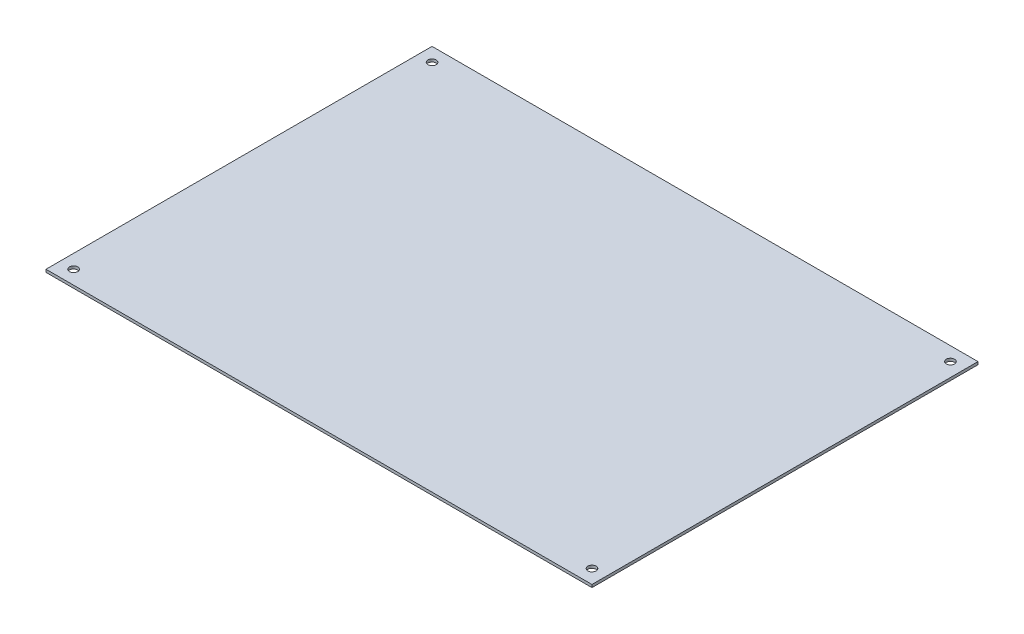
SolidWorks part; units mm, degrees
material "Copper"
ref_plane "Front Plane" through (0, 0, 0) normal (0, 0, 1) x (1, 0, 0)
ref_plane "Top Plane" through (0, 0, 0) normal (0, 1, 0) x (1, 0, 0)
ref_plane "Right Plane" through (0, 0, 0) normal (1, 0, 0) x (0, 0, -1)
sketch "Sketch1" plane through (0, 0, 0) normal (0, 1, 0) x (1, 0, 0)
  line L1 (148.5, -105) -> (-148.5, -105)
  line L2 (148.5, -105) -> (148.5, 105)
  line L3 (148.5, 105) -> (-148.5, 105)
  line L4 (-148.5, -105) -> (-148.5, 105)
  line L5 (148.5, -105) -> (-148.5, 105) construction
  line L6 (148.5, 105) -> (-148.5, -105) construction
  point P0 (0, 0)
  dimension "D1" = 297
  dimension "D2" = 210
extrude "Boss-Extrude1" add sketch "Sketch1" along normal blind 1.5
sketch "Sketch2" plane through (0, 1.5, 0) normal (0, 1, 0) x (1, 0, 0)
  line L0 (-101.7102, 6.397) -> (-102.7298, 6.397)
  line L1 (-102.7298, 6.397) -> (-103.109, 6.0178)
  line L2 (-103.109, 6.0178) -> (-103.109, 3.9822)
  line L3 (-103.109, 3.9822) -> (-102.7298, 3.603)
  line L4 (-102.7298, 3.603) -> (-101.7102, 3.603)
  line L5 (-101.7102, 3.603) -> (-101.331, 3.9822)
  line L6 (-101.331, 3.9822) -> (-101.331, 6.0178)
  line L7 (-101.331, 6.0178) -> (-101.7102, 6.397)
  line L8 (-104.2502, 6.397) -> (-105.2698, 6.397)
  line L9 (-105.2698, 6.397) -> (-105.649, 6.0178)
  line L10 (-105.649, 6.0178) -> (-105.649, 3.9822)
  line L11 (-105.649, 3.9822) -> (-105.2698, 3.603)
  line L12 (-105.2698, 3.603) -> (-104.2502, 3.603)
  line L13 (-104.2502, 3.603) -> (-103.871, 3.9822)
  line L14 (-103.871, 3.9822) -> (-103.871, 6.0178)
  line L15 (-103.871, 6.0178) -> (-104.2502, 6.397)
  line L16 (-106.7902, 6.397) -> (-107.8098, 6.397)
  line L17 (-107.8098, 6.397) -> (-108.189, 6.0178)
  line L18 (-108.189, 6.0178) -> (-108.189, 3.9822)
  line L19 (-108.189, 3.9822) -> (-107.8098, 3.603)
  line L20 (-107.8098, 3.603) -> (-106.7902, 3.603)
  line L21 (-106.7902, 3.603) -> (-106.411, 3.9822)
  line L22 (-106.411, 3.9822) -> (-106.411, 6.0178)
  line L23 (-106.411, 6.0178) -> (-106.7902, 6.397)
  line L24 (-109.3302, 6.397) -> (-110.3498, 6.397)
  line L25 (-110.3498, 6.397) -> (-110.729, 6.0178)
  line L26 (-110.729, 6.0178) -> (-110.729, 3.9822)
  line L27 (-110.729, 3.9822) -> (-110.3498, 3.603)
  line L28 (-110.3498, 3.603) -> (-109.3302, 3.603)
  line L29 (-109.3302, 3.603) -> (-108.951, 3.9822)
  line L30 (-108.951, 3.9822) -> (-108.951, 6.0178)
  line L31 (-108.951, 6.0178) -> (-109.3302, 6.397)
  line L32 (-111.8702, 6.397) -> (-112.8898, 6.397)
  line L33 (-112.8898, 6.397) -> (-113.269, 6.0178)
  line L34 (-113.269, 6.0178) -> (-113.269, 3.9822)
  line L35 (-113.269, 3.9822) -> (-112.8898, 3.603)
  line L36 (-112.8898, 3.603) -> (-111.8702, 3.603)
  line L37 (-111.8702, 3.603) -> (-111.491, 3.9822)
  line L38 (-111.491, 3.9822) -> (-111.491, 6.0178)
  line L39 (-111.491, 6.0178) -> (-111.8702, 6.397)
  line L40 (-114.4102, 6.397) -> (-115.4298, 6.397)
  line L41 (-115.4298, 6.397) -> (-115.809, 6.0178)
  line L42 (-115.809, 6.0178) -> (-115.809, 3.9822)
  line L43 (-115.809, 3.9822) -> (-115.4298, 3.603)
  line L44 (-115.4298, 3.603) -> (-114.4102, 3.603)
  line L45 (-114.4102, 3.603) -> (-114.031, 3.9822)
  line L46 (-114.031, 3.9822) -> (-114.031, 6.0178)
  line L47 (-114.031, 6.0178) -> (-114.4102, 6.397)
  line L48 (-116.9502, 6.397) -> (-117.9698, 6.397)
  line L49 (-117.9698, 6.397) -> (-118.349, 6.0178)
  line L50 (-118.349, 6.0178) -> (-118.349, 3.9822)
  line L51 (-118.349, 3.9822) -> (-117.9698, 3.603)
  line L52 (-117.9698, 3.603) -> (-116.9502, 3.603)
  line L53 (-116.9502, 3.603) -> (-116.571, 3.9822)
  line L54 (-116.571, 3.9822) -> (-116.571, 6.0178)
  line L55 (-116.571, 6.0178) -> (-116.9502, 6.397)
  line L56 (-119.4902, 6.397) -> (-120.5098, 6.397)
  line L57 (-120.5098, 6.397) -> (-120.889, 6.0178)
  line L58 (-120.889, 6.0178) -> (-120.889, 3.9822)
  line L59 (-120.889, 3.9822) -> (-120.5098, 3.603)
  line L60 (-120.5098, 3.603) -> (-119.4902, 3.603)
  line L61 (-119.4902, 3.603) -> (-119.111, 3.9822)
  line L62 (-119.111, 3.9822) -> (-119.111, 6.0178)
  line L63 (-119.111, 6.0178) -> (-119.4902, 6.397)
  line L64 (-97.6498, 6.397) -> (-96.6302, 6.397)
  line L65 (-96.6302, 6.397) -> (-96.251, 6.0178)
  line L66 (-96.251, 6.0178) -> (-96.251, 3.9822)
  line L67 (-96.251, 3.9822) -> (-96.6302, 3.603)
  line L68 (-96.6302, 3.603) -> (-97.6498, 3.603)
  line L69 (-97.6498, 3.603) -> (-98.029, 3.9822)
  line L70 (-98.029, 3.9822) -> (-98.029, 6.0178)
  line L71 (-98.029, 6.0178) -> (-97.6498, 6.397)
  line L72 (-95.1098, 6.397) -> (-94.0902, 6.397)
  line L73 (-94.0902, 6.397) -> (-93.711, 6.0178)
  line L74 (-93.711, 6.0178) -> (-93.711, 3.9822)
  line L75 (-93.711, 3.9822) -> (-94.0902, 3.603)
  line L76 (-94.0902, 3.603) -> (-95.1098, 3.603)
  line L77 (-95.1098, 3.603) -> (-95.489, 3.9822)
  line L78 (-95.489, 3.9822) -> (-95.489, 6.0178)
  line L79 (-95.489, 6.0178) -> (-95.1098, 6.397)
  line L80 (-92.5698, 6.397) -> (-91.5502, 6.397)
  line L81 (-91.5502, 6.397) -> (-91.171, 6.0178)
  line L82 (-91.171, 6.0178) -> (-91.171, 3.9822)
  line L83 (-91.171, 3.9822) -> (-91.5502, 3.603)
  line L84 (-91.5502, 3.603) -> (-92.5698, 3.603)
  line L85 (-92.5698, 3.603) -> (-92.949, 3.9822)
  line L86 (-92.949, 3.9822) -> (-92.949, 6.0178)
  line L87 (-92.949, 6.0178) -> (-92.5698, 6.397)
  line L88 (-90.0298, 6.397) -> (-89.0102, 6.397)
  line L89 (-89.0102, 6.397) -> (-88.631, 6.0178)
  line L90 (-88.631, 6.0178) -> (-88.631, 3.9822)
  line L91 (-88.631, 3.9822) -> (-89.0102, 3.603)
  line L92 (-89.0102, 3.603) -> (-90.0298, 3.603)
  line L93 (-90.0298, 3.603) -> (-90.409, 3.9822)
  line L94 (-90.409, 3.9822) -> (-90.409, 6.0178)
  line L95 (-90.409, 6.0178) -> (-90.0298, 6.397)
  line L96 (-87.4898, 6.397) -> (-86.4702, 6.397)
  line L97 (-86.4702, 6.397) -> (-86.091, 6.0178)
  line L98 (-86.091, 6.0178) -> (-86.091, 3.9822)
  line L99 (-86.091, 3.9822) -> (-86.4702, 3.603)
  line L100 (-86.4702, 3.603) -> (-87.4898, 3.603)
  line L101 (-87.4898, 3.603) -> (-87.869, 3.9822)
  line L102 (-87.869, 3.9822) -> (-87.869, 6.0178)
  line L103 (-87.869, 6.0178) -> (-87.4898, 6.397)
  line L104 (-84.9498, 6.397) -> (-83.9302, 6.397)
  line L105 (-83.9302, 6.397) -> (-83.551, 6.0178)
  line L106 (-83.551, 6.0178) -> (-83.551, 3.9822)
  line L107 (-83.551, 3.9822) -> (-83.9302, 3.603)
  line L108 (-83.9302, 3.603) -> (-84.9498, 3.603)
  line L109 (-84.9498, 3.603) -> (-85.329, 3.9822)
  line L110 (-85.329, 3.9822) -> (-85.329, 6.0178)
  line L111 (-85.329, 6.0178) -> (-84.9498, 6.397)
  line L112 (-83.9302, -41.863) -> (-84.9498, -41.863)
  line L113 (-84.9498, -41.863) -> (-85.329, -42.2422)
  line L114 (-85.329, -42.2422) -> (-85.329, -44.2778)
  line L115 (-85.329, -44.2778) -> (-84.9498, -44.657)
  line L116 (-84.9498, -44.657) -> (-83.9302, -44.657)
  line L117 (-83.9302, -44.657) -> (-83.551, -44.2778)
  line L118 (-83.551, -44.2778) -> (-83.551, -42.2422)
  line L119 (-83.551, -42.2422) -> (-83.9302, -41.863)
  line L120 (-86.4702, -41.863) -> (-87.4898, -41.863)
  line L121 (-87.4898, -41.863) -> (-87.869, -42.2422)
  line L122 (-87.869, -42.2422) -> (-87.869, -44.2778)
  line L123 (-87.869, -44.2778) -> (-87.4898, -44.657)
  line L124 (-87.4898, -44.657) -> (-86.4702, -44.657)
  line L125 (-86.4702, -44.657) -> (-86.091, -44.2778)
  line L126 (-86.091, -44.2778) -> (-86.091, -42.2422)
  line L127 (-86.091, -42.2422) -> (-86.4702, -41.863)
  line L128 (-89.0102, -41.863) -> (-90.0298, -41.863)
  line L129 (-90.0298, -41.863) -> (-90.409, -42.2422)
  line L130 (-90.409, -42.2422) -> (-90.409, -44.2778)
  line L131 (-90.409, -44.2778) -> (-90.0298, -44.657)
  line L132 (-90.0298, -44.657) -> (-89.0102, -44.657)
  line L133 (-89.0102, -44.657) -> (-88.631, -44.2778)
  line L134 (-88.631, -44.2778) -> (-88.631, -42.2422)
  line L135 (-88.631, -42.2422) -> (-89.0102, -41.863)
  line L136 (-91.5502, -41.863) -> (-92.5698, -41.863)
  line L137 (-92.5698, -41.863) -> (-92.949, -42.2422)
  line L138 (-92.949, -42.2422) -> (-92.949, -44.2778)
  line L139 (-92.949, -44.2778) -> (-92.5698, -44.657)
  line L140 (-92.5698, -44.657) -> (-91.5502, -44.657)
  line L141 (-91.5502, -44.657) -> (-91.171, -44.2778)
  line L142 (-91.171, -44.2778) -> (-91.171, -42.2422)
  line L143 (-91.171, -42.2422) -> (-91.5502, -41.863)
  line L144 (-94.0902, -41.863) -> (-95.1098, -41.863)
  line L145 (-95.1098, -41.863) -> (-95.489, -42.2422)
  line L146 (-95.489, -42.2422) -> (-95.489, -44.2778)
  line L147 (-95.489, -44.2778) -> (-95.1098, -44.657)
  line L148 (-95.1098, -44.657) -> (-94.0902, -44.657)
  line L149 (-94.0902, -44.657) -> (-93.711, -44.2778)
  line L150 (-93.711, -44.2778) -> (-93.711, -42.2422)
  line L151 (-93.711, -42.2422) -> (-94.0902, -41.863)
  line L152 (-96.6302, -41.863) -> (-97.6498, -41.863)
  line L153 (-97.6498, -41.863) -> (-98.029, -42.2422)
  line L154 (-98.029, -42.2422) -> (-98.029, -44.2778)
  line L155 (-98.029, -44.2778) -> (-97.6498, -44.657)
  line L156 (-97.6498, -44.657) -> (-96.6302, -44.657)
  line L157 (-96.6302, -44.657) -> (-96.251, -44.2778)
  line L158 (-96.251, -44.2778) -> (-96.251, -42.2422)
  line L159 (-96.251, -42.2422) -> (-96.6302, -41.863)
  line L160 (-99.1702, -41.863) -> (-100.1898, -41.863)
  line L161 (-100.1898, -41.863) -> (-100.569, -42.2422)
  line L162 (-100.569, -42.2422) -> (-100.569, -44.2778)
  line L163 (-100.569, -44.2778) -> (-100.1898, -44.657)
  line L164 (-100.1898, -44.657) -> (-99.1702, -44.657)
  line L165 (-99.1702, -44.657) -> (-98.791, -44.2778)
  line L166 (-98.791, -44.2778) -> (-98.791, -42.2422)
  line L167 (-98.791, -42.2422) -> (-99.1702, -41.863)
  line L168 (-101.7102, -41.863) -> (-102.7298, -41.863)
  line L169 (-102.7298, -41.863) -> (-103.109, -42.2422)
  line L170 (-103.109, -42.2422) -> (-103.109, -44.2778)
  line L171 (-103.109, -44.2778) -> (-102.7298, -44.657)
  line L172 (-102.7298, -44.657) -> (-101.7102, -44.657)
  line L173 (-101.7102, -44.657) -> (-101.331, -44.2778)
  line L174 (-101.331, -44.2778) -> (-101.331, -42.2422)
  line L175 (-101.331, -42.2422) -> (-101.7102, -41.863)
  line L176 (-105.5202, -41.863) -> (-106.5398, -41.863)
  line L177 (-106.5398, -41.863) -> (-106.919, -42.2422)
  line L178 (-106.919, -42.2422) -> (-106.919, -44.2778)
  line L179 (-106.919, -44.2778) -> (-106.5398, -44.657)
  line L180 (-106.5398, -44.657) -> (-105.5202, -44.657)
  line L181 (-105.5202, -44.657) -> (-105.141, -44.2778)
  line L182 (-105.141, -44.2778) -> (-105.141, -42.2422)
  line L183 (-105.141, -42.2422) -> (-105.5202, -41.863)
  line L184 (-108.0602, -41.863) -> (-109.0798, -41.863)
  line L185 (-109.0798, -41.863) -> (-109.459, -42.2422)
  line L186 (-109.459, -42.2422) -> (-109.459, -44.2778)
  line L187 (-109.459, -44.2778) -> (-109.0798, -44.657)
  line L188 (-109.0798, -44.657) -> (-108.0602, -44.657)
  line L189 (-108.0602, -44.657) -> (-107.681, -44.2778)
  line L190 (-107.681, -44.2778) -> (-107.681, -42.2422)
  line L191 (-107.681, -42.2422) -> (-108.0602, -41.863)
  line L192 (-110.6002, -41.863) -> (-111.6198, -41.863)
  line L193 (-111.6198, -41.863) -> (-111.999, -42.2422)
  line L194 (-111.999, -42.2422) -> (-111.999, -44.2778)
  line L195 (-111.999, -44.2778) -> (-111.6198, -44.657)
  line L196 (-111.6198, -44.657) -> (-110.6002, -44.657)
  line L197 (-110.6002, -44.657) -> (-110.221, -44.2778)
  line L198 (-110.221, -44.2778) -> (-110.221, -42.2422)
  line L199 (-110.221, -42.2422) -> (-110.6002, -41.863)
  line L200 (-113.1402, -41.863) -> (-114.1598, -41.863)
  line L201 (-114.1598, -41.863) -> (-114.539, -42.2422)
  line L202 (-114.539, -42.2422) -> (-114.539, -44.2778)
  line L203 (-114.539, -44.2778) -> (-114.1598, -44.657)
  line L204 (-114.1598, -44.657) -> (-113.1402, -44.657)
  line L205 (-113.1402, -44.657) -> (-112.761, -44.2778)
  line L206 (-112.761, -44.2778) -> (-112.761, -42.2422)
  line L207 (-112.761, -42.2422) -> (-113.1402, -41.863)
  line L208 (-115.6802, -41.863) -> (-116.6998, -41.863)
  line L209 (-116.6998, -41.863) -> (-117.079, -42.2422)
  line L210 (-117.079, -42.2422) -> (-117.079, -44.2778)
  line L211 (-117.079, -44.2778) -> (-116.6998, -44.657)
  line L212 (-116.6998, -44.657) -> (-115.6802, -44.657)
  line L213 (-115.6802, -44.657) -> (-115.301, -44.2778)
  line L214 (-115.301, -44.2778) -> (-115.301, -42.2422)
  line L215 (-115.301, -42.2422) -> (-115.6802, -41.863)
  line L216 (-118.2202, -41.863) -> (-119.2398, -41.863)
  line L217 (-119.2398, -41.863) -> (-119.619, -42.2422)
  line L218 (-119.619, -42.2422) -> (-119.619, -44.2778)
  line L219 (-119.619, -44.2778) -> (-119.2398, -44.657)
  line L220 (-119.2398, -44.657) -> (-118.2202, -44.657)
  line L221 (-118.2202, -44.657) -> (-117.841, -44.2778)
  line L222 (-117.841, -44.2778) -> (-117.841, -42.2422)
  line L223 (-117.841, -42.2422) -> (-118.2202, -41.863)
  line L224 (-120.7602, -41.863) -> (-121.7798, -41.863)
  line L225 (-121.7798, -41.863) -> (-122.159, -42.2422)
  line L226 (-122.159, -42.2422) -> (-122.159, -44.2778)
  line L227 (-122.159, -44.2778) -> (-121.7798, -44.657)
  line L228 (-121.7798, -44.657) -> (-120.7602, -44.657)
  line L229 (-120.7602, -44.657) -> (-120.381, -44.2778)
  line L230 (-120.381, -44.2778) -> (-120.381, -42.2422)
  line L231 (-120.381, -42.2422) -> (-120.7602, -41.863)
  line L232 (-123.3002, -41.863) -> (-124.3198, -41.863)
  line L233 (-124.3198, -41.863) -> (-124.699, -42.2422)
  line L234 (-124.699, -42.2422) -> (-124.699, -44.2778)
  line L235 (-124.699, -44.2778) -> (-124.3198, -44.657)
  line L236 (-124.3198, -44.657) -> (-123.3002, -44.657)
  line L237 (-123.3002, -44.657) -> (-122.921, -44.2778)
  line L238 (-122.921, -44.2778) -> (-122.921, -42.2422)
  line L239 (-122.921, -42.2422) -> (-123.3002, -41.863)
  line L240 (-125.8402, -41.863) -> (-126.8598, -41.863)
  line L241 (-126.8598, -41.863) -> (-127.239, -42.2422)
  line L242 (-127.239, -42.2422) -> (-127.239, -44.2778)
  line L243 (-127.239, -44.2778) -> (-126.8598, -44.657)
  line L244 (-126.8598, -44.657) -> (-125.8402, -44.657)
  line L245 (-125.8402, -44.657) -> (-125.461, -44.2778)
  line L246 (-125.461, -44.2778) -> (-125.461, -42.2422)
  line L247 (-125.461, -42.2422) -> (-125.8402, -41.863)
  line L248 (-128.3802, -41.863) -> (-129.3998, -41.863)
  line L249 (-129.3998, -41.863) -> (-129.779, -42.2422)
  line L250 (-129.779, -42.2422) -> (-129.779, -44.2778)
  line L251 (-129.779, -44.2778) -> (-129.3998, -44.657)
  line L252 (-129.3998, -44.657) -> (-128.3802, -44.657)
  line L253 (-128.3802, -44.657) -> (-128.001, -44.2778)
  line L254 (-128.001, -44.2778) -> (-128.001, -42.2422)
  line L255 (-128.001, -42.2422) -> (-128.3802, -41.863)
  line L256 (-4.887, -62.244) -> (-4.887, -64.276)
  line L257 (-4.887, -64.276) -> (-4.8895, -64.302)
  line L258 (-4.8895, -64.302) -> (-4.8968, -64.326)
  line L259 (-4.8968, -64.326) -> (-4.9083, -64.3476)
  line L260 (-4.9083, -64.3476) -> (-4.9237, -64.3663)
  line L261 (-4.9237, -64.3663) -> (-4.9424, -64.3817)
  line L262 (-4.9424, -64.3817) -> (-4.964, -64.3932)
  line L263 (-4.964, -64.3932) -> (-4.988, -64.4005)
  line L264 (-4.988, -64.4005) -> (-5.014, -64.403)
  line L265 (-5.014, -64.403) -> (-7.046, -64.403)
  line L266 (-7.046, -64.403) -> (-7.072, -64.4005)
  line L267 (-7.072, -64.4005) -> (-7.096, -64.3932)
  line L268 (-7.096, -64.3932) -> (-7.1176, -64.3817)
  line L269 (-7.1176, -64.3817) -> (-7.1363, -64.3663)
  line L270 (-7.1363, -64.3663) -> (-7.1516, -64.3476)
  line L271 (-7.1516, -64.3476) -> (-7.1632, -64.326)
  line L272 (-7.1632, -64.326) -> (-7.1705, -64.302)
  line L273 (-7.1705, -64.302) -> (-7.173, -64.276)
  line L274 (-7.173, -64.276) -> (-7.173, -62.244)
  line L275 (-7.173, -62.244) -> (-7.1705, -62.218)
  line L276 (-7.1705, -62.218) -> (-7.1632, -62.194)
  line L277 (-7.1632, -62.194) -> (-7.1516, -62.1724)
  line L278 (-7.1516, -62.1724) -> (-7.1363, -62.1537)
  line L279 (-7.1363, -62.1537) -> (-7.1176, -62.1384)
  line L280 (-7.1176, -62.1384) -> (-7.096, -62.1268)
  line L281 (-7.096, -62.1268) -> (-7.072, -62.1195)
  line L282 (-7.072, -62.1195) -> (-7.046, -62.117)
  line L283 (-7.046, -62.117) -> (-5.014, -62.117)
  line L284 (-5.014, -62.117) -> (-4.988, -62.1195)
  line L285 (-4.988, -62.1195) -> (-4.964, -62.1268)
  line L286 (-4.964, -62.1268) -> (-4.9424, -62.1384)
  line L287 (-4.9424, -62.1384) -> (-4.9237, -62.1537)
  line L288 (-4.9237, -62.1537) -> (-4.9083, -62.1724)
  line L289 (-4.9083, -62.1724) -> (-4.8968, -62.194)
  line L290 (-4.8968, -62.194) -> (-4.8895, -62.218)
  line L291 (-4.8895, -62.218) -> (-4.887, -62.244)
  line L292 (-4.887, -64.784) -> (-4.887, -66.816)
  line L293 (-4.887, -66.816) -> (-4.8895, -66.842)
  line L294 (-4.8895, -66.842) -> (-4.8968, -66.866)
  line L295 (-4.8968, -66.866) -> (-4.9083, -66.8876)
  line L296 (-4.9083, -66.8876) -> (-4.9237, -66.9063)
  line L297 (-4.9237, -66.9063) -> (-4.9424, -66.9217)
  line L298 (-4.9424, -66.9217) -> (-4.964, -66.9332)
  line L299 (-4.964, -66.9332) -> (-4.988, -66.9405)
  line L300 (-4.988, -66.9405) -> (-5.014, -66.943)
  line L301 (-5.014, -66.943) -> (-7.046, -66.943)
  line L302 (-7.046, -66.943) -> (-7.072, -66.9405)
  line L303 (-7.072, -66.9405) -> (-7.096, -66.9332)
  line L304 (-7.096, -66.9332) -> (-7.1176, -66.9217)
  line L305 (-7.1176, -66.9217) -> (-7.1363, -66.9063)
  line L306 (-7.1363, -66.9063) -> (-7.1516, -66.8876)
  line L307 (-7.1516, -66.8876) -> (-7.1632, -66.866)
  line L308 (-7.1632, -66.866) -> (-7.1705, -66.842)
  line L309 (-7.1705, -66.842) -> (-7.173, -66.816)
  line L310 (-7.173, -66.816) -> (-7.173, -64.784)
  line L311 (-7.173, -64.784) -> (-7.1705, -64.758)
  line L312 (-7.1705, -64.758) -> (-7.1632, -64.734)
  line L313 (-7.1632, -64.734) -> (-7.1516, -64.7124)
  line L314 (-7.1516, -64.7124) -> (-7.1363, -64.6937)
  line L315 (-7.1363, -64.6937) -> (-7.1176, -64.6784)
  line L316 (-7.1176, -64.6784) -> (-7.096, -64.6668)
  line L317 (-7.096, -64.6668) -> (-7.072, -64.6595)
  line L318 (-7.072, -64.6595) -> (-7.046, -64.657)
  line L319 (-7.046, -64.657) -> (-5.014, -64.657)
  line L320 (-5.014, -64.657) -> (-4.988, -64.6595)
  line L321 (-4.988, -64.6595) -> (-4.964, -64.6668)
  line L322 (-4.964, -64.6668) -> (-4.9424, -64.6784)
  line L323 (-4.9424, -64.6784) -> (-4.9237, -64.6937)
  line L324 (-4.9237, -64.6937) -> (-4.9083, -64.7124)
  line L325 (-4.9083, -64.7124) -> (-4.8968, -64.734)
  line L326 (-4.8968, -64.734) -> (-4.8895, -64.758)
  line L327 (-4.8895, -64.758) -> (-4.887, -64.784)
  line L328 (15.113, -62.244) -> (15.113, -64.276)
  line L329 (15.113, -64.276) -> (15.1105, -64.302)
  line L330 (15.1105, -64.302) -> (15.1032, -64.326)
  line L331 (15.1032, -64.326) -> (15.0916, -64.3476)
  line L332 (15.0916, -64.3476) -> (15.0763, -64.3663)
  line L333 (15.0763, -64.3663) -> (15.0576, -64.3817)
  line L334 (15.0576, -64.3817) -> (15.036, -64.3932)
  line L335 (15.036, -64.3932) -> (15.012, -64.4005)
  line L336 (15.012, -64.4005) -> (14.986, -64.403)
  line L337 (14.986, -64.403) -> (12.954, -64.403)
  line L338 (12.954, -64.403) -> (12.928, -64.4005)
  line L339 (12.928, -64.4005) -> (12.904, -64.3932)
  line L340 (12.904, -64.3932) -> (12.8824, -64.3817)
  line L341 (12.8824, -64.3817) -> (12.8637, -64.3663)
  line L342 (12.8637, -64.3663) -> (12.8484, -64.3476)
  line L343 (12.8484, -64.3476) -> (12.8368, -64.326)
  line L344 (12.8368, -64.326) -> (12.8295, -64.302)
  line L345 (12.8295, -64.302) -> (12.827, -64.276)
  line L346 (12.827, -64.276) -> (12.827, -62.244)
  line L347 (12.827, -62.244) -> (12.8295, -62.218)
  line L348 (12.8295, -62.218) -> (12.8368, -62.194)
  line L349 (12.8368, -62.194) -> (12.8484, -62.1724)
  line L350 (12.8484, -62.1724) -> (12.8637, -62.1537)
  line L351 (12.8637, -62.1537) -> (12.8824, -62.1384)
  line L352 (12.8824, -62.1384) -> (12.904, -62.1268)
  line L353 (12.904, -62.1268) -> (12.928, -62.1195)
  line L354 (12.928, -62.1195) -> (12.954, -62.117)
  line L355 (12.954, -62.117) -> (14.986, -62.117)
  line L356 (14.986, -62.117) -> (15.012, -62.1195)
  line L357 (15.012, -62.1195) -> (15.036, -62.1268)
  line L358 (15.036, -62.1268) -> (15.0576, -62.1384)
  line L359 (15.0576, -62.1384) -> (15.0763, -62.1537)
  line L360 (15.0763, -62.1537) -> (15.0916, -62.1724)
  line L361 (15.0916, -62.1724) -> (15.1032, -62.194)
  line L362 (15.1032, -62.194) -> (15.1105, -62.218)
  line L363 (15.1105, -62.218) -> (15.113, -62.244)
  line L364 (15.113, -64.784) -> (15.113, -66.816)
  line L365 (15.113, -66.816) -> (15.1105, -66.842)
  line L366 (15.1105, -66.842) -> (15.1032, -66.866)
  line L367 (15.1032, -66.866) -> (15.0916, -66.8876)
  line L368 (15.0916, -66.8876) -> (15.0763, -66.9063)
  line L369 (15.0763, -66.9063) -> (15.0576, -66.9217)
  line L370 (15.0576, -66.9217) -> (15.036, -66.9332)
  line L371 (15.036, -66.9332) -> (15.012, -66.9405)
  line L372 (15.012, -66.9405) -> (14.986, -66.943)
  line L373 (14.986, -66.943) -> (12.954, -66.943)
  line L374 (12.954, -66.943) -> (12.928, -66.9405)
  line L375 (12.928, -66.9405) -> (12.904, -66.9332)
  line L376 (12.904, -66.9332) -> (12.8824, -66.9217)
  line L377 (12.8824, -66.9217) -> (12.8637, -66.9063)
  line L378 (12.8637, -66.9063) -> (12.8484, -66.8876)
  line L379 (12.8484, -66.8876) -> (12.8368, -66.866)
  line L380 (12.8368, -66.866) -> (12.8295, -66.842)
  line L381 (12.8295, -66.842) -> (12.827, -66.816)
  line L382 (12.827, -66.816) -> (12.827, -64.784)
  line L383 (12.827, -64.784) -> (12.8295, -64.758)
  line L384 (12.8295, -64.758) -> (12.8368, -64.734)
  line L385 (12.8368, -64.734) -> (12.8484, -64.7124)
  line L386 (12.8484, -64.7124) -> (12.8637, -64.6937)
  line L387 (12.8637, -64.6937) -> (12.8824, -64.6784)
  line L388 (12.8824, -64.6784) -> (12.904, -64.6668)
  line L389 (12.904, -64.6668) -> (12.928, -64.6595)
  line L390 (12.928, -64.6595) -> (12.954, -64.657)
  line L391 (12.954, -64.657) -> (14.986, -64.657)
  line L392 (14.986, -64.657) -> (15.012, -64.6595)
  line L393 (15.012, -64.6595) -> (15.036, -64.6668)
  line L394 (15.036, -64.6668) -> (15.0576, -64.6784)
  line L395 (15.0576, -64.6784) -> (15.0763, -64.6937)
  line L396 (15.0763, -64.6937) -> (15.0916, -64.7124)
  line L397 (15.0916, -64.7124) -> (15.1032, -64.734)
  line L398 (15.1032, -64.734) -> (15.1105, -64.758)
  line L399 (15.1105, -64.758) -> (15.113, -64.784)
  line L400 (35.113, -62.244) -> (35.113, -64.276)
  line L401 (35.113, -64.276) -> (35.1105, -64.302)
  line L402 (35.1105, -64.302) -> (35.1032, -64.326)
  line L403 (35.1032, -64.326) -> (35.0916, -64.3476)
  line L404 (35.0916, -64.3476) -> (35.0763, -64.3663)
  line L405 (35.0763, -64.3663) -> (35.0576, -64.3817)
  line L406 (35.0576, -64.3817) -> (35.036, -64.3932)
  line L407 (35.036, -64.3932) -> (35.012, -64.4005)
  line L408 (35.012, -64.4005) -> (34.986, -64.403)
  line L409 (34.986, -64.403) -> (32.954, -64.403)
  line L410 (32.954, -64.403) -> (32.928, -64.4005)
  line L411 (32.928, -64.4005) -> (32.904, -64.3932)
  line L412 (32.904, -64.3932) -> (32.8824, -64.3817)
  line L413 (32.8824, -64.3817) -> (32.8637, -64.3663)
  line L414 (32.8637, -64.3663) -> (32.8483, -64.3476)
  line L415 (32.8483, -64.3476) -> (32.8368, -64.326)
  line L416 (32.8368, -64.326) -> (32.8295, -64.302)
  line L417 (32.8295, -64.302) -> (32.827, -64.276)
  line L418 (32.827, -64.276) -> (32.827, -62.244)
  line L419 (32.827, -62.244) -> (32.8295, -62.218)
  line L420 (32.8295, -62.218) -> (32.8368, -62.194)
  line L421 (32.8368, -62.194) -> (32.8483, -62.1724)
  line L422 (32.8483, -62.1724) -> (32.8637, -62.1537)
  line L423 (32.8637, -62.1537) -> (32.8824, -62.1384)
  line L424 (32.8824, -62.1384) -> (32.904, -62.1268)
  line L425 (32.904, -62.1268) -> (32.928, -62.1195)
  line L426 (32.928, -62.1195) -> (32.954, -62.117)
  line L427 (32.954, -62.117) -> (34.986, -62.117)
  line L428 (34.986, -62.117) -> (35.012, -62.1195)
  line L429 (35.012, -62.1195) -> (35.036, -62.1268)
  line L430 (35.036, -62.1268) -> (35.0576, -62.1384)
  line L431 (35.0576, -62.1384) -> (35.0763, -62.1537)
  line L432 (35.0763, -62.1537) -> (35.0916, -62.1724)
  line L433 (35.0916, -62.1724) -> (35.1032, -62.194)
  line L434 (35.1032, -62.194) -> (35.1105, -62.218)
  line L435 (35.1105, -62.218) -> (35.113, -62.244)
  line L436 (35.113, -64.784) -> (35.113, -66.816)
  line L437 (35.113, -66.816) -> (35.1105, -66.842)
  line L438 (35.1105, -66.842) -> (35.1032, -66.866)
  line L439 (35.1032, -66.866) -> (35.0916, -66.8876)
  line L440 (35.0916, -66.8876) -> (35.0763, -66.9063)
  line L441 (35.0763, -66.9063) -> (35.0576, -66.9217)
  line L442 (35.0576, -66.9217) -> (35.036, -66.9332)
  line L443 (35.036, -66.9332) -> (35.012, -66.9405)
  line L444 (35.012, -66.9405) -> (34.986, -66.943)
  line L445 (34.986, -66.943) -> (32.954, -66.943)
  line L446 (32.954, -66.943) -> (32.928, -66.9405)
  line L447 (32.928, -66.9405) -> (32.904, -66.9332)
  line L448 (32.904, -66.9332) -> (32.8824, -66.9217)
  line L449 (32.8824, -66.9217) -> (32.8637, -66.9063)
  line L450 (32.8637, -66.9063) -> (32.8483, -66.8876)
  line L451 (32.8483, -66.8876) -> (32.8368, -66.866)
  line L452 (32.8368, -66.866) -> (32.8295, -66.842)
  line L453 (32.8295, -66.842) -> (32.827, -66.816)
  line L454 (32.827, -66.816) -> (32.827, -64.784)
  line L455 (32.827, -64.784) -> (32.8295, -64.758)
  line L456 (32.8295, -64.758) -> (32.8368, -64.734)
  line L457 (32.8368, -64.734) -> (32.8483, -64.7124)
  line L458 (32.8483, -64.7124) -> (32.8637, -64.6937)
  line L459 (32.8637, -64.6937) -> (32.8824, -64.6784)
  line L460 (32.8824, -64.6784) -> (32.904, -64.6668)
  line L461 (32.904, -64.6668) -> (32.928, -64.6595)
  line L462 (32.928, -64.6595) -> (32.954, -64.657)
  line L463 (32.954, -64.657) -> (34.986, -64.657)
  line L464 (34.986, -64.657) -> (35.012, -64.6595)
  line L465 (35.012, -64.6595) -> (35.036, -64.6668)
  line L466 (35.036, -64.6668) -> (35.0576, -64.6784)
  line L467 (35.0576, -64.6784) -> (35.0763, -64.6937)
  line L468 (35.0763, -64.6937) -> (35.0916, -64.7124)
  line L469 (35.0916, -64.7124) -> (35.1032, -64.734)
  line L470 (35.1032, -64.734) -> (35.1105, -64.758)
  line L471 (35.1105, -64.758) -> (35.113, -64.784)
  line L472 (55.113, -62.244) -> (55.113, -64.276)
  line L473 (55.113, -64.276) -> (55.1105, -64.302)
  line L474 (55.1105, -64.302) -> (55.1032, -64.326)
  line L475 (55.1032, -64.326) -> (55.0917, -64.3476)
  line L476 (55.0917, -64.3476) -> (55.0763, -64.3663)
  line L477 (55.0763, -64.3663) -> (55.0576, -64.3817)
  line L478 (55.0576, -64.3817) -> (55.036, -64.3932)
  line L479 (55.036, -64.3932) -> (55.012, -64.4005)
  line L480 (55.012, -64.4005) -> (54.986, -64.403)
  line L481 (54.986, -64.403) -> (52.954, -64.403)
  line L482 (52.954, -64.403) -> (52.928, -64.4005)
  line L483 (52.928, -64.4005) -> (52.904, -64.3932)
  line L484 (52.904, -64.3932) -> (52.8824, -64.3817)
  line L485 (52.8824, -64.3817) -> (52.8637, -64.3663)
  line L486 (52.8637, -64.3663) -> (52.8484, -64.3476)
  line L487 (52.8484, -64.3476) -> (52.8368, -64.326)
  line L488 (52.8368, -64.326) -> (52.8295, -64.302)
  line L489 (52.8295, -64.302) -> (52.827, -64.276)
  line L490 (52.827, -64.276) -> (52.827, -62.244)
  line L491 (52.827, -62.244) -> (52.8295, -62.218)
  line L492 (52.8295, -62.218) -> (52.8368, -62.194)
  line L493 (52.8368, -62.194) -> (52.8484, -62.1724)
  line L494 (52.8484, -62.1724) -> (52.8637, -62.1537)
  line L495 (52.8637, -62.1537) -> (52.8824, -62.1384)
  line L496 (52.8824, -62.1384) -> (52.904, -62.1268)
  line L497 (52.904, -62.1268) -> (52.928, -62.1195)
  line L498 (52.928, -62.1195) -> (52.954, -62.117)
  line L499 (52.954, -62.117) -> (54.986, -62.117)
  line L500 (54.986, -62.117) -> (55.012, -62.1195)
  line L501 (55.012, -62.1195) -> (55.036, -62.1268)
  line L502 (55.036, -62.1268) -> (55.0576, -62.1384)
  line L503 (55.0576, -62.1384) -> (55.0763, -62.1537)
  line L504 (55.0763, -62.1537) -> (55.0917, -62.1724)
  line L505 (55.0917, -62.1724) -> (55.1032, -62.194)
  line L506 (55.1032, -62.194) -> (55.1105, -62.218)
  line L507 (55.1105, -62.218) -> (55.113, -62.244)
  line L508 (55.113, -64.784) -> (55.113, -66.816)
  line L509 (55.113, -66.816) -> (55.1105, -66.842)
  line L510 (55.1105, -66.842) -> (55.1032, -66.866)
  line L511 (55.1032, -66.866) -> (55.0917, -66.8876)
  line L512 (55.0917, -66.8876) -> (55.0763, -66.9063)
  line L513 (55.0763, -66.9063) -> (55.0576, -66.9217)
  line L514 (55.0576, -66.9217) -> (55.036, -66.9332)
  line L515 (55.036, -66.9332) -> (55.012, -66.9405)
  line L516 (55.012, -66.9405) -> (54.986, -66.943)
  line L517 (54.986, -66.943) -> (52.954, -66.943)
  line L518 (52.954, -66.943) -> (52.928, -66.9405)
  line L519 (52.928, -66.9405) -> (52.904, -66.9332)
  line L520 (52.904, -66.9332) -> (52.8824, -66.9217)
  line L521 (52.8824, -66.9217) -> (52.8637, -66.9063)
  line L522 (52.8637, -66.9063) -> (52.8484, -66.8876)
  line L523 (52.8484, -66.8876) -> (52.8368, -66.866)
  line L524 (52.8368, -66.866) -> (52.8295, -66.842)
  line L525 (52.8295, -66.842) -> (52.827, -66.816)
  line L526 (52.827, -66.816) -> (52.827, -64.784)
  line L527 (52.827, -64.784) -> (52.8295, -64.758)
  line L528 (52.8295, -64.758) -> (52.8368, -64.734)
  line L529 (52.8368, -64.734) -> (52.8484, -64.7124)
  line L530 (52.8484, -64.7124) -> (52.8637, -64.6937)
  line L531 (52.8637, -64.6937) -> (52.8824, -64.6784)
  line L532 (52.8824, -64.6784) -> (52.904, -64.6668)
  line L533 (52.904, -64.6668) -> (52.928, -64.6595)
  line L534 (52.928, -64.6595) -> (52.954, -64.657)
  line L535 (52.954, -64.657) -> (54.986, -64.657)
  line L536 (54.986, -64.657) -> (55.012, -64.6595)
  line L537 (55.012, -64.6595) -> (55.036, -64.6668)
  line L538 (55.036, -64.6668) -> (55.0576, -64.6784)
  line L539 (55.0576, -64.6784) -> (55.0763, -64.6937)
  line L540 (55.0763, -64.6937) -> (55.0917, -64.7124)
  line L541 (55.0917, -64.7124) -> (55.1032, -64.734)
  line L542 (55.1032, -64.734) -> (55.1105, -64.758)
  line L543 (55.1105, -64.758) -> (55.113, -64.784)
  line L544 (75.113, -62.244) -> (75.113, -64.276)
  line L545 (75.113, -64.276) -> (75.1105, -64.302)
  line L546 (75.1105, -64.302) -> (75.1032, -64.326)
  line L547 (75.1032, -64.326) -> (75.0916, -64.3476)
  line L548 (75.0916, -64.3476) -> (75.0763, -64.3663)
  line L549 (75.0763, -64.3663) -> (75.0576, -64.3817)
  line L550 (75.0576, -64.3817) -> (75.036, -64.3932)
  line L551 (75.036, -64.3932) -> (75.012, -64.4005)
  line L552 (75.012, -64.4005) -> (74.986, -64.403)
  line L553 (74.986, -64.403) -> (72.954, -64.403)
  line L554 (72.954, -64.403) -> (72.928, -64.4005)
  line L555 (72.928, -64.4005) -> (72.904, -64.3932)
  line L556 (72.904, -64.3932) -> (72.8824, -64.3817)
  line L557 (72.8824, -64.3817) -> (72.8637, -64.3663)
  line L558 (72.8637, -64.3663) -> (72.8483, -64.3476)
  line L559 (72.8483, -64.3476) -> (72.8368, -64.326)
  line L560 (72.8368, -64.326) -> (72.8295, -64.302)
  line L561 (72.8295, -64.302) -> (72.827, -64.276)
  line L562 (72.827, -64.276) -> (72.827, -62.244)
  line L563 (72.827, -62.244) -> (72.8295, -62.218)
  line L564 (72.8295, -62.218) -> (72.8368, -62.194)
  line L565 (72.8368, -62.194) -> (72.8483, -62.1724)
  line L566 (72.8483, -62.1724) -> (72.8637, -62.1537)
  line L567 (72.8637, -62.1537) -> (72.8824, -62.1384)
  line L568 (72.8824, -62.1384) -> (72.904, -62.1268)
  line L569 (72.904, -62.1268) -> (72.928, -62.1195)
  line L570 (72.928, -62.1195) -> (72.954, -62.117)
  line L571 (72.954, -62.117) -> (74.986, -62.117)
  line L572 (74.986, -62.117) -> (75.012, -62.1195)
  line L573 (75.012, -62.1195) -> (75.036, -62.1268)
  line L574 (75.036, -62.1268) -> (75.0576, -62.1384)
  line L575 (75.0576, -62.1384) -> (75.0763, -62.1537)
  line L576 (75.0763, -62.1537) -> (75.0916, -62.1724)
  line L577 (75.0916, -62.1724) -> (75.1032, -62.194)
  line L578 (75.1032, -62.194) -> (75.1105, -62.218)
  line L579 (75.1105, -62.218) -> (75.113, -62.244)
  line L580 (75.113, -64.784) -> (75.113, -66.816)
  line L581 (75.113, -66.816) -> (75.1105, -66.842)
  line L582 (75.1105, -66.842) -> (75.1032, -66.866)
  line L583 (75.1032, -66.866) -> (75.0916, -66.8876)
  line L584 (75.0916, -66.8876) -> (75.0763, -66.9063)
  line L585 (75.0763, -66.9063) -> (75.0576, -66.9217)
  line L586 (75.0576, -66.9217) -> (75.036, -66.9332)
  line L587 (75.036, -66.9332) -> (75.012, -66.9405)
  line L588 (75.012, -66.9405) -> (74.986, -66.943)
  line L589 (74.986, -66.943) -> (72.954, -66.943)
  line L590 (72.954, -66.943) -> (72.928, -66.9405)
  line L591 (72.928, -66.9405) -> (72.904, -66.9332)
  line L592 (72.904, -66.9332) -> (72.8824, -66.9217)
  line L593 (72.8824, -66.9217) -> (72.8637, -66.9063)
  line L594 (72.8637, -66.9063) -> (72.8483, -66.8876)
  line L595 (72.8483, -66.8876) -> (72.8368, -66.866)
  line L596 (72.8368, -66.866) -> (72.8295, -66.842)
  line L597 (72.8295, -66.842) -> (72.827, -66.816)
  line L598 (72.827, -66.816) -> (72.827, -64.784)
  line L599 (72.827, -64.784) -> (72.8295, -64.758)
  line L600 (72.8295, -64.758) -> (72.8368, -64.734)
  line L601 (72.8368, -64.734) -> (72.8483, -64.7124)
  line L602 (72.8483, -64.7124) -> (72.8637, -64.6937)
  line L603 (72.8637, -64.6937) -> (72.8824, -64.6784)
  line L604 (72.8824, -64.6784) -> (72.904, -64.6668)
  line L605 (72.904, -64.6668) -> (72.928, -64.6595)
  line L606 (72.928, -64.6595) -> (72.954, -64.657)
  line L607 (72.954, -64.657) -> (74.986, -64.657)
  line L608 (74.986, -64.657) -> (75.012, -64.6595)
  line L609 (75.012, -64.6595) -> (75.036, -64.6668)
  line L610 (75.036, -64.6668) -> (75.0576, -64.6784)
  line L611 (75.0576, -64.6784) -> (75.0763, -64.6937)
  line L612 (75.0763, -64.6937) -> (75.0916, -64.7124)
  line L613 (75.0916, -64.7124) -> (75.1032, -64.734)
  line L614 (75.1032, -64.734) -> (75.1105, -64.758)
  line L615 (75.1105, -64.758) -> (75.113, -64.784)
  line L616 (95.113, -62.244) -> (95.113, -64.276)
  line L617 (95.113, -64.276) -> (95.1105, -64.302)
  line L618 (95.1105, -64.302) -> (95.1032, -64.326)
  line L619 (95.1032, -64.326) -> (95.0917, -64.3476)
  line L620 (95.0917, -64.3476) -> (95.0763, -64.3663)
  line L621 (95.0763, -64.3663) -> (95.0576, -64.3817)
  line L622 (95.0576, -64.3817) -> (95.036, -64.3932)
  line L623 (95.036, -64.3932) -> (95.012, -64.4005)
  line L624 (95.012, -64.4005) -> (94.986, -64.403)
  line L625 (94.986, -64.403) -> (92.954, -64.403)
  line L626 (92.954, -64.403) -> (92.928, -64.4005)
  line L627 (92.928, -64.4005) -> (92.904, -64.3932)
  line L628 (92.904, -64.3932) -> (92.8824, -64.3817)
  line L629 (92.8824, -64.3817) -> (92.8637, -64.3663)
  line L630 (92.8637, -64.3663) -> (92.8484, -64.3476)
  line L631 (92.8484, -64.3476) -> (92.8368, -64.326)
  line L632 (92.8368, -64.326) -> (92.8295, -64.302)
  line L633 (92.8295, -64.302) -> (92.827, -64.276)
  line L634 (92.827, -64.276) -> (92.827, -62.244)
  line L635 (92.827, -62.244) -> (92.8295, -62.218)
  line L636 (92.8295, -62.218) -> (92.8368, -62.194)
  line L637 (92.8368, -62.194) -> (92.8484, -62.1724)
  line L638 (92.8484, -62.1724) -> (92.8637, -62.1537)
  line L639 (92.8637, -62.1537) -> (92.8824, -62.1384)
  line L640 (92.8824, -62.1384) -> (92.904, -62.1268)
  line L641 (92.904, -62.1268) -> (92.928, -62.1195)
  line L642 (92.928, -62.1195) -> (92.954, -62.117)
  line L643 (92.954, -62.117) -> (94.986, -62.117)
  line L644 (94.986, -62.117) -> (95.012, -62.1195)
  line L645 (95.012, -62.1195) -> (95.036, -62.1268)
  line L646 (95.036, -62.1268) -> (95.0576, -62.1384)
  line L647 (95.0576, -62.1384) -> (95.0763, -62.1537)
  line L648 (95.0763, -62.1537) -> (95.0917, -62.1724)
  line L649 (95.0917, -62.1724) -> (95.1032, -62.194)
  line L650 (95.1032, -62.194) -> (95.1105, -62.218)
  line L651 (95.1105, -62.218) -> (95.113, -62.244)
  line L652 (95.113, -64.784) -> (95.113, -66.816)
  line L653 (95.113, -66.816) -> (95.1105, -66.842)
  line L654 (95.1105, -66.842) -> (95.1032, -66.866)
  line L655 (95.1032, -66.866) -> (95.0917, -66.8876)
  line L656 (95.0917, -66.8876) -> (95.0763, -66.9063)
  line L657 (95.0763, -66.9063) -> (95.0576, -66.9217)
  line L658 (95.0576, -66.9217) -> (95.036, -66.9332)
  line L659 (95.036, -66.9332) -> (95.012, -66.9405)
  line L660 (95.012, -66.9405) -> (94.986, -66.943)
  line L661 (94.986, -66.943) -> (92.954, -66.943)
  line L662 (92.954, -66.943) -> (92.928, -66.9405)
  line L663 (92.928, -66.9405) -> (92.904, -66.9332)
  line L664 (92.904, -66.9332) -> (92.8824, -66.9217)
  line L665 (92.8824, -66.9217) -> (92.8637, -66.9063)
  line L666 (92.8637, -66.9063) -> (92.8484, -66.8876)
  line L667 (92.8484, -66.8876) -> (92.8368, -66.866)
  line L668 (92.8368, -66.866) -> (92.8295, -66.842)
  line L669 (92.8295, -66.842) -> (92.827, -66.816)
  line L670 (92.827, -66.816) -> (92.827, -64.784)
  line L671 (92.827, -64.784) -> (92.8295, -64.758)
  line L672 (92.8295, -64.758) -> (92.8368, -64.734)
  line L673 (92.8368, -64.734) -> (92.8484, -64.7124)
  line L674 (92.8484, -64.7124) -> (92.8637, -64.6937)
  line L675 (92.8637, -64.6937) -> (92.8824, -64.6784)
  line L676 (92.8824, -64.6784) -> (92.904, -64.6668)
  line L677 (92.904, -64.6668) -> (92.928, -64.6595)
  line L678 (92.928, -64.6595) -> (92.954, -64.657)
  line L679 (92.954, -64.657) -> (94.986, -64.657)
  line L680 (94.986, -64.657) -> (95.012, -64.6595)
  line L681 (95.012, -64.6595) -> (95.036, -64.6668)
  line L682 (95.036, -64.6668) -> (95.0576, -64.6784)
  line L683 (95.0576, -64.6784) -> (95.0763, -64.6937)
  line L684 (95.0763, -64.6937) -> (95.0917, -64.7124)
  line L685 (95.0917, -64.7124) -> (95.1032, -64.734)
  line L686 (95.1032, -64.734) -> (95.1105, -64.758)
  line L687 (95.1105, -64.758) -> (95.113, -64.784)
  line L688 (44.5598, 68.137) -> (43.5402, 68.137)
  line L689 (43.5402, 68.137) -> (43.161, 67.7578)
  line L690 (43.161, 67.7578) -> (43.161, 65.7222)
  line L691 (43.161, 65.7222) -> (43.5402, 65.343)
  line L692 (43.5402, 65.343) -> (44.5598, 65.343)
  line L693 (44.5598, 65.343) -> (44.939, 65.7222)
  line L694 (44.939, 65.7222) -> (44.939, 67.7578)
  line L695 (44.939, 67.7578) -> (44.5598, 68.137)
  line L696 (42.0198, 68.137) -> (41.0002, 68.137)
  line L697 (41.0002, 68.137) -> (40.621, 67.7578)
  line L698 (40.621, 67.7578) -> (40.621, 65.7222)
  line L699 (40.621, 65.7222) -> (41.0002, 65.343)
  line L700 (41.0002, 65.343) -> (42.0198, 65.343)
  line L701 (42.0198, 65.343) -> (42.399, 65.7222)
  line L702 (42.399, 65.7222) -> (42.399, 67.7578)
  line L703 (42.399, 67.7578) -> (42.0198, 68.137)
  line L704 (39.4798, 68.137) -> (38.4602, 68.137)
  line L705 (38.4602, 68.137) -> (38.081, 67.7578)
  line L706 (38.081, 67.7578) -> (38.081, 65.7222)
  line L707 (38.081, 65.7222) -> (38.4602, 65.343)
  line L708 (38.4602, 65.343) -> (39.4798, 65.343)
  line L709 (39.4798, 65.343) -> (39.859, 65.7222)
  line L710 (39.859, 65.7222) -> (39.859, 67.7578)
  line L711 (39.859, 67.7578) -> (39.4798, 68.137)
  line L712 (36.9398, 68.137) -> (35.9202, 68.137)
  line L713 (35.9202, 68.137) -> (35.541, 67.7578)
  line L714 (35.541, 67.7578) -> (35.541, 65.7222)
  line L715 (35.541, 65.7222) -> (35.9202, 65.343)
  line L716 (35.9202, 65.343) -> (36.9398, 65.343)
  line L717 (36.9398, 65.343) -> (37.319, 65.7222)
  line L718 (37.319, 65.7222) -> (37.319, 67.7578)
  line L719 (37.319, 67.7578) -> (36.9398, 68.137)
  line L720 (34.3998, 68.137) -> (33.3802, 68.137)
  line L721 (33.3802, 68.137) -> (33.001, 67.7578)
  line L722 (33.001, 67.7578) -> (33.001, 65.7222)
  line L723 (33.001, 65.7222) -> (33.3802, 65.343)
  line L724 (33.3802, 65.343) -> (34.3998, 65.343)
  line L725 (34.3998, 65.343) -> (34.779, 65.7222)
  line L726 (34.779, 65.7222) -> (34.779, 67.7578)
  line L727 (34.779, 67.7578) -> (34.3998, 68.137)
  line L728 (31.8598, 68.137) -> (30.8402, 68.137)
  line L729 (30.8402, 68.137) -> (30.461, 67.7578)
  line L730 (30.461, 67.7578) -> (30.461, 65.7222)
  line L731 (30.461, 65.7222) -> (30.8402, 65.343)
  line L732 (30.8402, 65.343) -> (31.8598, 65.343)
  line L733 (31.8598, 65.343) -> (32.239, 65.7222)
  line L734 (32.239, 65.7222) -> (32.239, 67.7578)
  line L735 (32.239, 67.7578) -> (31.8598, 68.137)
  line L736 (29.3198, 68.137) -> (28.3002, 68.137)
  line L737 (28.3002, 68.137) -> (27.921, 67.7578)
  line L738 (27.921, 67.7578) -> (27.921, 65.7222)
  line L739 (27.921, 65.7222) -> (28.3002, 65.343)
  line L740 (28.3002, 65.343) -> (29.3198, 65.343)
  line L741 (29.3198, 65.343) -> (29.699, 65.7222)
  line L742 (29.699, 65.7222) -> (29.699, 67.7578)
  line L743 (29.699, 67.7578) -> (29.3198, 68.137)
  line L744 (26.7798, 68.137) -> (25.7602, 68.137)
  line L745 (25.7602, 68.137) -> (25.381, 67.7578)
  line L746 (25.381, 67.7578) -> (25.381, 65.7222)
  line L747 (25.381, 65.7222) -> (25.7602, 65.343)
  line L748 (25.7602, 65.343) -> (26.7798, 65.343)
  line L749 (26.7798, 65.343) -> (27.159, 65.7222)
  line L750 (27.159, 65.7222) -> (27.159, 67.7578)
  line L751 (27.159, 67.7578) -> (26.7798, 68.137)
  line L752 (24.2798, 68.137) -> (23.2602, 68.137)
  line L753 (23.2602, 68.137) -> (22.881, 67.7578)
  line L754 (22.881, 67.7578) -> (22.881, 65.7222)
  line L755 (22.881, 65.7222) -> (23.2602, 65.343)
  line L756 (23.2602, 65.343) -> (24.2798, 65.343)
  line L757 (24.2798, 65.343) -> (24.659, 65.7222)
  line L758 (24.659, 65.7222) -> (24.659, 67.7578)
  line L759 (24.659, 67.7578) -> (24.2798, 68.137)
  line L760 (21.7398, 68.137) -> (20.7202, 68.137)
  line L761 (20.7202, 68.137) -> (20.341, 67.7578)
  line L762 (20.341, 67.7578) -> (20.341, 65.7222)
  line L763 (20.341, 65.7222) -> (20.7202, 65.343)
  line L764 (20.7202, 65.343) -> (21.7398, 65.343)
  line L765 (21.7398, 65.343) -> (22.119, 65.7222)
  line L766 (22.119, 65.7222) -> (22.119, 67.7578)
  line L767 (22.119, 67.7578) -> (21.7398, 68.137)
  line L768 (19.1998, 68.137) -> (18.1802, 68.137)
  line L769 (18.1802, 68.137) -> (17.801, 67.7578)
  line L770 (17.801, 67.7578) -> (17.801, 65.7222)
  line L771 (17.801, 65.7222) -> (18.1802, 65.343)
  line L772 (18.1802, 65.343) -> (19.1998, 65.343)
  line L773 (19.1998, 65.343) -> (19.579, 65.7222)
  line L774 (19.579, 65.7222) -> (19.579, 67.7578)
  line L775 (19.579, 67.7578) -> (19.1998, 68.137)
  line L776 (16.6598, 68.137) -> (15.6402, 68.137)
  line L777 (15.6402, 68.137) -> (15.261, 67.7578)
  line L778 (15.261, 67.7578) -> (15.261, 65.7222)
  line L779 (15.261, 65.7222) -> (15.6402, 65.343)
  line L780 (15.6402, 65.343) -> (16.6598, 65.343)
  line L781 (16.6598, 65.343) -> (17.039, 65.7222)
  line L782 (17.039, 65.7222) -> (17.039, 67.7578)
  line L783 (17.039, 67.7578) -> (16.6598, 68.137)
  line L784 (14.1198, 68.137) -> (13.1002, 68.137)
  line L785 (13.1002, 68.137) -> (12.721, 67.7578)
  line L786 (12.721, 67.7578) -> (12.721, 65.7222)
  line L787 (12.721, 65.7222) -> (13.1002, 65.343)
  line L788 (13.1002, 65.343) -> (14.1198, 65.343)
  line L789 (14.1198, 65.343) -> (14.499, 65.7222)
  line L790 (14.499, 65.7222) -> (14.499, 67.7578)
  line L791 (14.499, 67.7578) -> (14.1198, 68.137)
  line L792 (11.5798, 68.137) -> (10.5602, 68.137)
  line L793 (10.5602, 68.137) -> (10.181, 67.7578)
  line L794 (10.181, 67.7578) -> (10.181, 65.7222)
  line L795 (10.181, 65.7222) -> (10.5602, 65.343)
  line L796 (10.5602, 65.343) -> (11.5798, 65.343)
  line L797 (11.5798, 65.343) -> (11.959, 65.7222)
  line L798 (11.959, 65.7222) -> (11.959, 67.7578)
  line L799 (11.959, 67.7578) -> (11.5798, 68.137)
  line L800 (9.0398, 68.137) -> (8.0202, 68.137)
  line L801 (8.0202, 68.137) -> (7.641, 67.7578)
  line L802 (7.641, 67.7578) -> (7.641, 65.7222)
  line L803 (7.641, 65.7222) -> (8.0202, 65.343)
  line L804 (8.0202, 65.343) -> (9.0398, 65.343)
  line L805 (9.0398, 65.343) -> (9.419, 65.7222)
  line L806 (9.419, 65.7222) -> (9.419, 67.7578)
  line L807 (9.419, 67.7578) -> (9.0398, 68.137)
  line L808 (6.4998, 68.137) -> (5.4802, 68.137)
  line L809 (5.4802, 68.137) -> (5.101, 67.7578)
  line L810 (5.101, 67.7578) -> (5.101, 65.7222)
  line L811 (5.101, 65.7222) -> (5.4802, 65.343)
  line L812 (5.4802, 65.343) -> (6.4998, 65.343)
  line L813 (6.4998, 65.343) -> (6.879, 65.7222)
  line L814 (6.879, 65.7222) -> (6.879, 67.7578)
  line L815 (6.879, 67.7578) -> (6.4998, 68.137)
  line L816 (-121.27, 3.095) -> (-100.95, 3.095)
  line L817 (-100.95, 3.095) -> (-100.95, 6.905)
  line L818 (-100.95, 6.905) -> (-121.27, 6.905)
  line L819 (-121.27, 6.905) -> (-121.27, 3.095)
  line L820 (-107.935, 7.159) -> (-114.412, 7.159) construction
  line L821 (-98.41, 3.095) -> (-83.17, 3.095)
  line L822 (-83.17, 3.095) -> (-83.17, 6.905)
  line L823 (-83.17, 6.905) -> (-98.41, 6.905)
  line L824 (-98.41, 6.905) -> (-98.41, 3.095)
  line L825 (-103.49, -45.165) -> (-83.17, -45.165)
  line L826 (-83.17, -45.165) -> (-83.17, -41.355)
  line L827 (-83.17, -41.355) -> (-103.49, -41.355)
  line L828 (-103.49, -41.355) -> (-103.49, -45.165)
  line L829 (-90.79, -41.101) -> (-95.4382, -41.101) construction
  line L830 (-130.16, -45.165) -> (-104.76, -45.165)
  line L831 (-104.76, -45.165) -> (-104.76, -41.355)
  line L832 (-104.76, -41.355) -> (-130.16, -41.355)
  line L833 (-130.16, -41.355) -> (-130.16, -45.165)
  line L834 (-114.285, -41.101) -> (-119.9619, -41.101) construction
  line L835 (-3.49, -61.355) -> (-3.49, -62.625)
  line L836 (-2.855, -61.99) -> (-4.125, -61.99)
  line L837 (-1.3818, -65.4825) -> (-1.3818, -63.4632) construction
  line L838 (16.51, -61.355) -> (16.51, -62.625)
  line L839 (17.145, -61.99) -> (15.875, -61.99)
  line L840 (18.6182, -65.4825) -> (18.6182, -63.0441) construction
  line L841 (36.51, -61.355) -> (36.51, -62.625)
  line L842 (37.145, -61.99) -> (35.875, -61.99)
  line L843 (38.6182, -65.4825) -> (38.6182, -63.0441) construction
  line L844 (56.51, -61.355) -> (56.51, -62.625)
  line L845 (57.145, -61.99) -> (55.875, -61.99)
  line L846 (58.6182, -65.4825) -> (58.6182, -63.0441) construction
  line L847 (76.51, -61.355) -> (76.51, -62.625)
  line L848 (77.145, -61.99) -> (75.875, -61.99)
  line L849 (78.6182, -65.4825) -> (78.6182, -63.0441) construction
  line L850 (96.51, -61.355) -> (96.51, -62.625)
  line L851 (97.145, -61.99) -> (95.875, -61.99)
  line L852 (98.6182, -65.4825) -> (98.6182, -63.0441) construction
  line L853 (-6.03, -47.03) -> (-6.03, -48.3)
  line L854 (-6.665, -53.38) -> (-5.395, -53.38)
  line L855 (-5.395, -53.38) -> (-5.395, -48.3)
  line L856 (-5.395, -48.3) -> (-6.665, -48.3)
  line L857 (-6.665, -48.3) -> (-6.665, -53.38)
  line L858 (-6.03, -53.38) -> (-6.03, -54.65)
  line L859 (-3.9218, -52.11) -> (-3.9218, -50.0907) construction
  line L860 (13.97, -47.03) -> (13.97, -48.3)
  line L861 (13.335, -53.38) -> (14.605, -53.38)
  line L862 (14.605, -53.38) -> (14.605, -48.3)
  line L863 (14.605, -48.3) -> (13.335, -48.3)
  line L864 (13.335, -48.3) -> (13.335, -53.38)
  line L865 (13.97, -53.38) -> (13.97, -54.65)
  line L866 (16.0782, -52.11) -> (16.0782, -49.6716) construction
  line L867 (33.97, -47.03) -> (33.97, -48.3)
  line L868 (33.335, -53.38) -> (34.605, -53.38)
  line L869 (34.605, -53.38) -> (34.605, -48.3)
  line L870 (34.605, -48.3) -> (33.335, -48.3)
  line L871 (33.335, -48.3) -> (33.335, -53.38)
  line L872 (33.97, -53.38) -> (33.97, -54.65)
  line L873 (36.0782, -52.11) -> (36.0782, -49.6716) construction
  line L874 (53.97, -47.03) -> (53.97, -48.3)
  line L875 (53.335, -53.38) -> (54.605, -53.38)
  line L876 (54.605, -53.38) -> (54.605, -48.3)
  line L877 (54.605, -48.3) -> (53.335, -48.3)
  line L878 (53.335, -48.3) -> (53.335, -53.38)
  line L879 (53.97, -53.38) -> (53.97, -54.65)
  line L880 (56.0782, -52.11) -> (56.0782, -49.6716) construction
  line L881 (73.97, -47.03) -> (73.97, -48.3)
  line L882 (73.335, -53.38) -> (74.605, -53.38)
  line L883 (74.605, -53.38) -> (74.605, -48.3)
  line L884 (74.605, -48.3) -> (73.335, -48.3)
  line L885 (73.335, -48.3) -> (73.335, -53.38)
  line L886 (73.97, -53.38) -> (73.97, -54.65)
  line L887 (76.0782, -52.11) -> (76.0782, -49.6716) construction
  line L888 (93.97, -47.03) -> (93.97, -48.3)
  line L889 (93.335, -53.38) -> (94.605, -53.38)
  line L890 (94.605, -53.38) -> (94.605, -48.3)
  line L891 (94.605, -48.3) -> (93.335, -48.3)
  line L892 (93.335, -48.3) -> (93.335, -53.38)
  line L893 (93.97, -53.38) -> (93.97, -54.65)
  line L894 (96.0782, -52.11) -> (96.0782, -49.6716) construction
  line L895 (25, 64.835) -> (45.32, 64.835)
  line L896 (45.32, 64.835) -> (45.32, 68.645)
  line L897 (45.32, 68.645) -> (25, 68.645)
  line L898 (25, 68.645) -> (25, 64.835)
  line L899 (37.7, 68.899) -> (33.2423, 68.899) construction
  line L900 (4.72, 64.835) -> (25.04, 64.835)
  line L901 (25.04, 64.835) -> (25.04, 68.645)
  line L902 (25.04, 68.645) -> (4.72, 68.645)
  line L903 (4.72, 68.645) -> (4.72, 64.835)
  line L904 (17.42, 68.899) -> (12.5432, 68.899) construction
  line L905 (107.66, 39.835) -> (115.28, 39.835)
  line L906 (115.28, 39.835) -> (115.28, 43.645)
  line L907 (115.28, 43.645) -> (107.66, 43.645)
  line L908 (107.66, 43.645) -> (107.66, 39.835)
  line L909 (111.47, 44.915) -> (111.47, 49.995)
  line L910 (110.2, 47.455) -> (112.74, 47.455)
  line L911 (115.2, 64.24) -> (113.93, 64.24)
  line L912 (108.85, 63.605) -> (113.93, 63.605)
  line L913 (113.93, 63.605) -> (113.93, 64.875)
  line L914 (113.93, 64.875) -> (108.85, 64.875)
  line L915 (108.85, 64.875) -> (108.85, 63.605)
  line L916 (108.85, 64.24) -> (107.58, 64.24)
  line L917 (-121.27, 3.095) -> (-100.95, 3.095)
  line L918 (-100.95, 3.095) -> (-100.95, 6.905)
  line L919 (-100.95, 6.905) -> (-121.27, 6.905)
  line L920 (-121.27, 6.905) -> (-121.27, 3.095)
  line L921 (-107.935, 7.159) -> (-114.412, 7.159) construction
  line L922 (-98.41, 3.095) -> (-83.17, 3.095)
  line L923 (-83.17, 3.095) -> (-83.17, 6.905)
  line L924 (-83.17, 6.905) -> (-98.41, 6.905)
  line L925 (-98.41, 6.905) -> (-98.41, 3.095)
  line L926 (-103.49, -45.165) -> (-83.17, -45.165)
  line L927 (-83.17, -45.165) -> (-83.17, -41.355)
  line L928 (-83.17, -41.355) -> (-103.49, -41.355)
  line L929 (-103.49, -41.355) -> (-103.49, -45.165)
  line L930 (-90.79, -41.101) -> (-95.4382, -41.101) construction
  line L931 (-130.16, -45.165) -> (-104.76, -45.165)
  line L932 (-104.76, -45.165) -> (-104.76, -41.355)
  line L933 (-104.76, -41.355) -> (-130.16, -41.355)
  line L934 (-130.16, -41.355) -> (-130.16, -45.165)
  line L935 (-114.285, -41.101) -> (-119.9619, -41.101) construction
  line L936 (-3.49, -61.355) -> (-3.49, -62.625)
  line L937 (-2.855, -61.99) -> (-4.125, -61.99)
  line L938 (-1.3818, -65.4825) -> (-1.3818, -63.4632) construction
  line L939 (16.51, -61.355) -> (16.51, -62.625)
  line L940 (17.145, -61.99) -> (15.875, -61.99)
  line L941 (18.6182, -65.4825) -> (18.6182, -63.0441) construction
  line L942 (36.51, -61.355) -> (36.51, -62.625)
  line L943 (37.145, -61.99) -> (35.875, -61.99)
  line L944 (38.6182, -65.4825) -> (38.6182, -63.0441) construction
  line L945 (56.51, -61.355) -> (56.51, -62.625)
  line L946 (57.145, -61.99) -> (55.875, -61.99)
  line L947 (58.6182, -65.4825) -> (58.6182, -63.0441) construction
  line L948 (76.51, -61.355) -> (76.51, -62.625)
  line L949 (77.145, -61.99) -> (75.875, -61.99)
  line L950 (78.6182, -65.4825) -> (78.6182, -63.0441) construction
  line L951 (96.51, -61.355) -> (96.51, -62.625)
  line L952 (97.145, -61.99) -> (95.875, -61.99)
  line L953 (98.6182, -65.4825) -> (98.6182, -63.0441) construction
  line L954 (-6.03, -47.03) -> (-6.03, -48.3)
  line L955 (-6.665, -53.38) -> (-5.395, -53.38)
  line L956 (-5.395, -53.38) -> (-5.395, -48.3)
  line L957 (-5.395, -48.3) -> (-6.665, -48.3)
  line L958 (-6.665, -48.3) -> (-6.665, -53.38)
  line L959 (-6.03, -53.38) -> (-6.03, -54.65)
  line L960 (-3.9218, -52.11) -> (-3.9218, -50.0907) construction
  line L961 (13.97, -47.03) -> (13.97, -48.3)
  line L962 (13.335, -53.38) -> (14.605, -53.38)
  line L963 (14.605, -53.38) -> (14.605, -48.3)
  line L964 (14.605, -48.3) -> (13.335, -48.3)
  line L965 (13.335, -48.3) -> (13.335, -53.38)
  line L966 (13.97, -53.38) -> (13.97, -54.65)
  line L967 (16.0782, -52.11) -> (16.0782, -49.6716) construction
  line L968 (33.97, -47.03) -> (33.97, -48.3)
  line L969 (33.335, -53.38) -> (34.605, -53.38)
  line L970 (34.605, -53.38) -> (34.605, -48.3)
  line L971 (34.605, -48.3) -> (33.335, -48.3)
  line L972 (33.335, -48.3) -> (33.335, -53.38)
  line L973 (33.97, -53.38) -> (33.97, -54.65)
  line L974 (36.0782, -52.11) -> (36.0782, -49.6716) construction
  line L975 (53.97, -47.03) -> (53.97, -48.3)
  line L976 (53.335, -53.38) -> (54.605, -53.38)
  line L977 (54.605, -53.38) -> (54.605, -48.3)
  line L978 (54.605, -48.3) -> (53.335, -48.3)
  line L979 (53.335, -48.3) -> (53.335, -53.38)
  line L980 (53.97, -53.38) -> (53.97, -54.65)
  line L981 (56.0782, -52.11) -> (56.0782, -49.6716) construction
  line L982 (73.97, -47.03) -> (73.97, -48.3)
  line L983 (73.335, -53.38) -> (74.605, -53.38)
  line L984 (74.605, -53.38) -> (74.605, -48.3)
  line L985 (74.605, -48.3) -> (73.335, -48.3)
  line L986 (73.335, -48.3) -> (73.335, -53.38)
  line L987 (73.97, -53.38) -> (73.97, -54.65)
  line L988 (76.0782, -52.11) -> (76.0782, -49.6716) construction
  line L989 (93.97, -47.03) -> (93.97, -48.3)
  line L990 (93.335, -53.38) -> (94.605, -53.38)
  line L991 (94.605, -53.38) -> (94.605, -48.3)
  line L992 (94.605, -48.3) -> (93.335, -48.3)
  line L993 (93.335, -48.3) -> (93.335, -53.38)
  line L994 (93.97, -53.38) -> (93.97, -54.65)
  line L995 (96.0782, -52.11) -> (96.0782, -49.6716) construction
  line L996 (25, 64.835) -> (45.32, 64.835)
  line L997 (45.32, 64.835) -> (45.32, 68.645)
  line L998 (45.32, 68.645) -> (25, 68.645)
  line L999 (25, 68.645) -> (25, 64.835)
  line L1000 (37.7, 68.899) -> (33.2423, 68.899) construction
  line L1001 (4.72, 64.835) -> (25.04, 64.835)
  line L1002 (25.04, 64.835) -> (25.04, 68.645)
  line L1003 (25.04, 68.645) -> (4.72, 68.645)
  line L1004 (4.72, 68.645) -> (4.72, 64.835)
  line L1005 (17.42, 68.899) -> (12.5432, 68.899) construction
  line L1006 (107.66, 39.835) -> (115.28, 39.835)
  line L1007 (115.28, 39.835) -> (115.28, 43.645)
  line L1008 (115.28, 43.645) -> (107.66, 43.645)
  line L1009 (107.66, 43.645) -> (107.66, 39.835)
  line L1010 (111.47, 44.915) -> (111.47, 49.995)
  line L1011 (110.2, 47.455) -> (112.74, 47.455)
  line L1012 (115.2, 64.24) -> (113.93, 64.24)
  line L1013 (108.85, 63.605) -> (113.93, 63.605)
  line L1014 (113.93, 63.605) -> (113.93, 64.875)
  line L1015 (113.93, 64.875) -> (108.85, 64.875)
  line L1016 (108.85, 64.875) -> (108.85, 63.605)
  line L1017 (108.85, 64.24) -> (107.58, 64.24)
  circle A0 centre (-6.03, -45.76) radius 0.508
  circle A1 centre (-6.03, -55.92) radius 0.508
  circle A2 centre (13.97, -45.76) radius 0.508
  circle A3 centre (13.97, -55.92) radius 0.508
  circle A4 centre (33.97, -45.76) radius 0.508
  circle A5 centre (33.97, -55.92) radius 0.508
  circle A6 centre (53.97, -45.76) radius 0.508
  circle A7 centre (53.97, -55.92) radius 0.508
  circle A8 centre (73.97, -45.76) radius 0.508
  circle A9 centre (73.97, -55.92) radius 0.508
  circle A10 centre (93.97, -45.76) radius 0.508
  circle A11 centre (93.97, -55.92) radius 0.508
  circle A12 centre (108.93, 41.74) radius 0.5715
  circle A13 centre (114.01, 41.74) radius 0.5715
  circle A14 centre (111.47, 41.74) radius 0.5715
  circle A15 centre (116.47, 64.24) radius 0.508
  circle A16 centre (106.31, 64.24) radius 0.508
  circle A17 centre (-141, 97.5) radius 1.651
  circle A18 centre (-141, -97.5) radius 1.651
  circle A19 centre (141, 97.5) radius 1.651
  circle A20 centre (141, -97.5) radius 1.651
  circle A21 centre (-6.03, -64.53) radius 2.54
  circle A22 centre (13.97, -64.53) radius 2.54
  circle A23 centre (33.97, -64.53) radius 2.54
  circle A24 centre (53.97, -64.53) radius 2.54
  circle A25 centre (73.97, -64.53) radius 2.54
  circle A26 centre (93.97, -64.53) radius 2.54
  circle A27 centre (111.47, 47.455) radius 3.81
  circle A28 centre (-6.03, -64.53) radius 2.54
  circle A29 centre (13.97, -64.53) radius 2.54
  circle A30 centre (33.97, -64.53) radius 2.54
  circle A31 centre (53.97, -64.53) radius 2.54
  circle A32 centre (73.97, -64.53) radius 2.54
  circle A33 centre (93.97, -64.53) radius 2.54
  circle A34 centre (111.47, 47.455) radius 3.81
  text T0 "A_PWR" font "SWTXT" height 1.2192
  text T1 "A" font "SWTXT" height 1.2192
  text T2 "D0_7" font "SWTXT" height 1.2192
  text T3 "D8_13" font "SWTXT" height 1.2192
  text T4 "D1" font "SWTXT" height 1.2192
  text T5 "D2" font "SWTXT" height 1.2192
  text T6 "D3" font "SWTXT" height 1.2192
  text T7 "D4" font "SWTXT" height 1.2192
  text T8 "D5" font "SWTXT" height 1.2192
  text T9 "D6" font "SWTXT" height 1.2192
  text T10 "R1" font "SWTXT" height 1.2192
  text T11 "R2" font "SWTXT" height 1.2192
  text T12 "R3" font "SWTXT" height 1.2192
  text T13 "R4" font "SWTXT" height 1.2192
  text T14 "R5" font "SWTXT" height 1.2192
  text T15 "R6" font "SWTXT" height 1.2192
  text T16 "LCD1" font "SWTXT" height 1.2192
  text T17 "LCD2" font "SWTXT" height 1.2192
  text T18 "BRT" font "SWTXT" height 1.2192
  text T19 "RLED" font "SWTXT" height 1.2192
  text T20 "A_PWR" font "SWTXT" height 1.2192
  text T21 "A" font "SWTXT" height 1.2192
  text T22 "D0_7" font "SWTXT" height 1.2192
  text T23 "D8_13" font "SWTXT" height 1.2192
  text T24 "D1" font "SWTXT" height 1.2192
  text T25 "D2" font "SWTXT" height 1.2192
  text T26 "D3" font "SWTXT" height 1.2192
  text T27 "D4" font "SWTXT" height 1.2192
  text T28 "D5" font "SWTXT" height 1.2192
  text T29 "D6" font "SWTXT" height 1.2192
  text T30 "R1" font "SWTXT" height 1.2192
  text T31 "R2" font "SWTXT" height 1.2192
  text T32 "R3" font "SWTXT" height 1.2192
  text T33 "R4" font "SWTXT" height 1.2192
  text T34 "R5" font "SWTXT" height 1.2192
  text T35 "R6" font "SWTXT" height 1.2192
  text T36 "LCD1" font "SWTXT" height 1.2192
  text T37 "LCD2" font "SWTXT" height 1.2192
  text T38 "BRT" font "SWTXT" height 1.2192
  text T39 "RLED" font "SWTXT" height 1.2192
hole_wizard "M4 Clearance Hole1" positions "Sketch3" profile "Sketch4" hole size "M4" standard "ANSI Metric" end condition through all
sketch "Sketch3" plane through (0, 1.5, 0) normal (0, 1, 0) x (1, 0, 0)
  point P0 (-141, 97.5)
  point P3 (-141, -97.5)
  point P6 (141, -97.5)
  point P9 (141, 97.5)
sketch "Sketch4" plane through (-141, 1.5, -97.5) normal (1, 0, 0) x (0, 0, 1)
  line L0 (0, 0) -> (0, 1.5)
  line L1 (0, 1.5) -> (2.25, 1.5)
  line L2 (2.25, 1.5) -> (2.25, 0)
  line L5 (2.25, 0) -> (0, 0)
  line L11 (0, -6.35) -> (0, 107.95) construction
  dimension "Thru Hole Dia." = 4.5
  dimension "Thru Hole Depth" = 1.5
